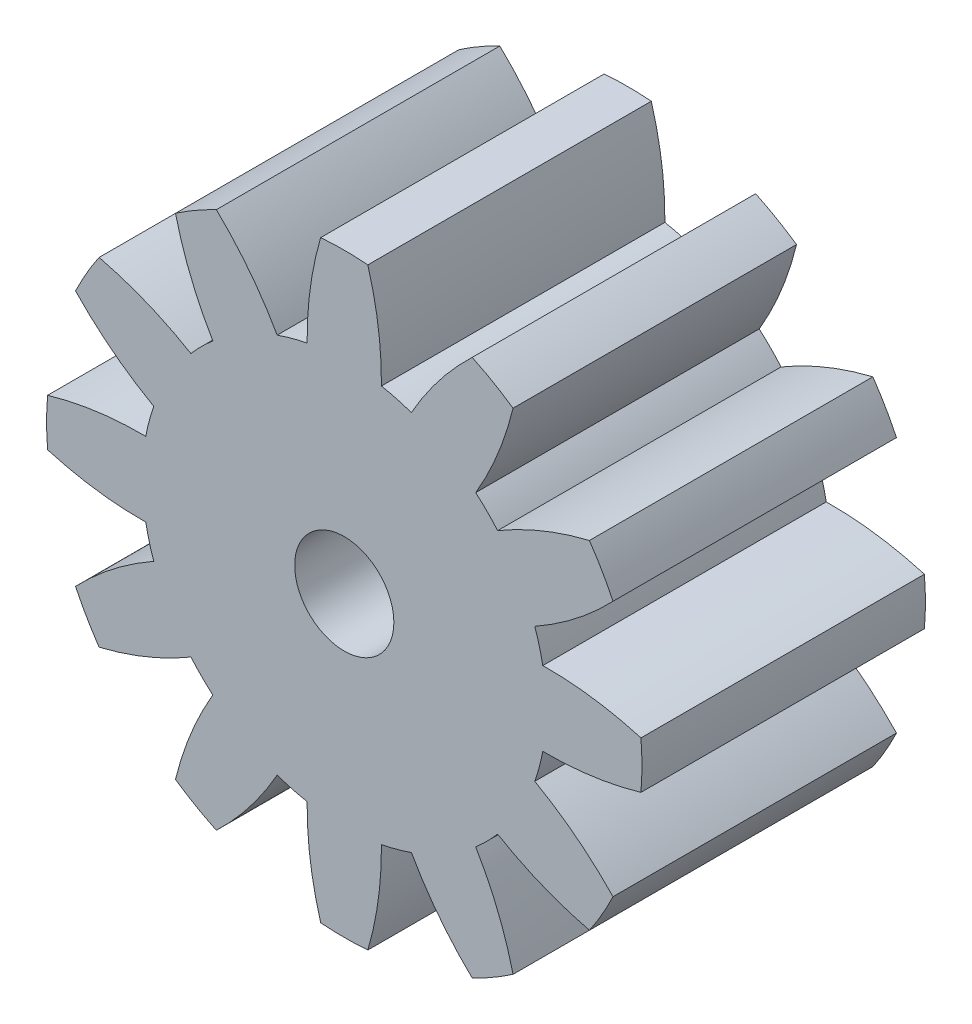
SolidWorks part; units mm, degrees
ref_plane "정면" through (0, 0, 0) normal (0, 0, 1) x (1, 0, 0)
ref_plane "윗면" through (0, 0, 0) normal (0, 1, 0) x (1, 0, 0)
ref_plane "우측면" through (0, 0, 0) normal (1, 0, 0) x (0, 0, -1)
sketch "스케치1" plane through (0, 0, 0) normal (0, 0, 1) x (1, 0, 0)
  line L0 (0, 0) -> (0, 2.1) construction
  line L1 (0, 0) -> (-0.2349, 1.7846) construction
  line L2 (-0.2349, 1.7846) -> (-0.1665, 2.0934) construction
  line L3 (-0.2349, 1.7846) -> (-0.3591, 0.0253) construction
  circle A0 centre (0, 0) radius 1.8 construction
  circle A1 centre (0, 0) radius 2.1 construction
  circle A2 centre (0, 0) radius 1.425 construction
  circle A3 centre (0, 0) radius 0.36 construction
  arc A4 (-0.1665, 2.0934) -> (-0.262, 1.4007) centre (2.1135, 1.426) ccw
  arc A5 (0.1665, 2.0934) -> (0.262, 1.4007) centre (-2.1135, 1.426) cw
  arc A6 (-0.1665, 2.0934) -> (0.1665, 2.0934) centre (0, 0) cw
  circle A40 centre (0, 0) radius 0.35
  arc A41 (1.1909, 1.7297) -> (0.9273, 1.082) centre (-1.1173, 2.2916) cw
  arc A42 (0.9025, 1.8962) -> (1.1909, 1.7297) centre (0, 0) cw
  arc A43 (0.9025, 1.8962) -> (0.4734, 1.3441) centre (2.5433, 0.1782) ccw
  arc A44 (1.8962, 0.9025) -> (1.3441, 0.4734) centre (0.1782, 2.5433) cw
  arc A45 (1.7297, 1.1909) -> (1.8962, 0.9025) centre (0, 0) cw
  arc A46 (1.7297, 1.1909) -> (1.082, 0.9273) centre (2.2916, -1.1173) ccw
  arc A47 (2.0934, -0.1665) -> (1.4007, -0.262) centre (1.426, 2.1135) cw
  arc A48 (2.0934, 0.1665) -> (2.0934, -0.1665) centre (0, 0) cw
  arc A49 (2.0934, 0.1665) -> (1.4007, 0.262) centre (1.426, -2.1135) ccw
  arc A50 (1.7297, -1.1909) -> (1.082, -0.9273) centre (2.2916, 1.1173) cw
  arc A51 (1.8962, -0.9025) -> (1.7297, -1.1909) centre (0, 0) cw
  arc A52 (1.8962, -0.9025) -> (1.3441, -0.4734) centre (0.1782, -2.5433) ccw
  arc A53 (0.9025, -1.8962) -> (0.4734, -1.3441) centre (2.5433, -0.1782) cw
  arc A54 (1.1909, -1.7297) -> (0.9025, -1.8962) centre (0, 0) cw
  arc A55 (1.1909, -1.7297) -> (0.9273, -1.082) centre (-1.1173, -2.2916) ccw
  arc A56 (-0.1665, -2.0934) -> (-0.262, -1.4007) centre (2.1135, -1.426) cw
  arc A57 (0.1665, -2.0934) -> (-0.1665, -2.0934) centre (0, 0) cw
  arc A58 (0.1665, -2.0934) -> (0.262, -1.4007) centre (-2.1135, -1.426) ccw
  arc A59 (-1.1909, -1.7297) -> (-0.9273, -1.082) centre (1.1173, -2.2916) cw
  arc A60 (-0.9025, -1.8962) -> (-1.1909, -1.7297) centre (0, 0) cw
  arc A61 (-0.9025, -1.8962) -> (-0.4734, -1.3441) centre (-2.5433, -0.1782) ccw
  arc A62 (-1.8962, -0.9025) -> (-1.3441, -0.4734) centre (-0.1782, -2.5433) cw
  arc A63 (-1.7297, -1.1909) -> (-1.8962, -0.9025) centre (0, 0) cw
  arc A64 (-1.7297, -1.1909) -> (-1.082, -0.9273) centre (-2.2916, 1.1173) ccw
  arc A66 (-2.0934, 0.1665) -> (-1.4007, 0.262) centre (-1.426, -2.1135) cw
  arc A67 (-2.0934, -0.1665) -> (-2.0934, 0.1665) centre (0, 0) cw
  arc A68 (-2.0934, -0.1665) -> (-1.4007, -0.262) centre (-1.426, 2.1135) ccw
  arc A69 (-1.7297, 1.1909) -> (-1.082, 0.9273) centre (-2.2916, -1.1173) cw
  arc A70 (-1.8962, 0.9025) -> (-1.7297, 1.1909) centre (0, 0) cw
  arc A71 (-1.8962, 0.9025) -> (-1.3441, 0.4734) centre (-0.1782, 2.5433) ccw
  arc A72 (-0.9025, 1.8962) -> (-0.4734, 1.3441) centre (-2.5433, 0.1782) cw
  arc A73 (-1.1909, 1.7297) -> (-0.9025, 1.8962) centre (0, 0) cw
  arc A74 (-1.1909, 1.7297) -> (-0.9273, 1.082) centre (1.1173, 2.2916) ccw
  arc A75 (-0.4734, 1.3441) -> (-0.262, 1.4007) centre (0, 0) cw
  arc A76 (0.262, 1.4007) -> (0.4734, 1.3441) centre (0, 0) cw
  arc A77 (0.9273, 1.082) -> (1.082, 0.9273) centre (0, 0) cw
  arc A78 (1.3441, 0.4734) -> (1.4007, 0.262) centre (0, 0) cw
  arc A79 (1.4007, -0.262) -> (1.3441, -0.4734) centre (0, 0) cw
  arc A80 (1.082, -0.9273) -> (0.9273, -1.082) centre (0, 0) cw
  arc A81 (0.4734, -1.3441) -> (0.262, -1.4007) centre (0, 0) cw
  arc A82 (-0.262, -1.4007) -> (-0.4734, -1.3441) centre (0, 0) cw
  arc A83 (-0.9273, -1.082) -> (-1.082, -0.9273) centre (0, 0) cw
  arc A84 (-1.3441, -0.4734) -> (-1.4007, -0.262) centre (0, 0) cw
  arc A85 (-1.4007, 0.262) -> (-1.3441, 0.4734) centre (0, 0) cw
  arc A86 (-1.082, 0.9273) -> (-0.9273, 1.082) centre (0, 0) cw
  point P67 (0, 0)
  point P84 (0, 0)
  point P89 (0, 0)
  point P113 (0, 0)
  dimension "D1" = 3.6
  dimension "D2" = 0.375
  dimension "D3" = 0.3
  dimension "D6" = 0.72
  dimension "D9" = 0.7
  dimension "D4" = 20
  dimension "D5" = 7.5
  dimension "D7" = 12
  dimension "D8" = 12
extrude "보스-돌출1" add sketch "스케치1" along normal blind 2
